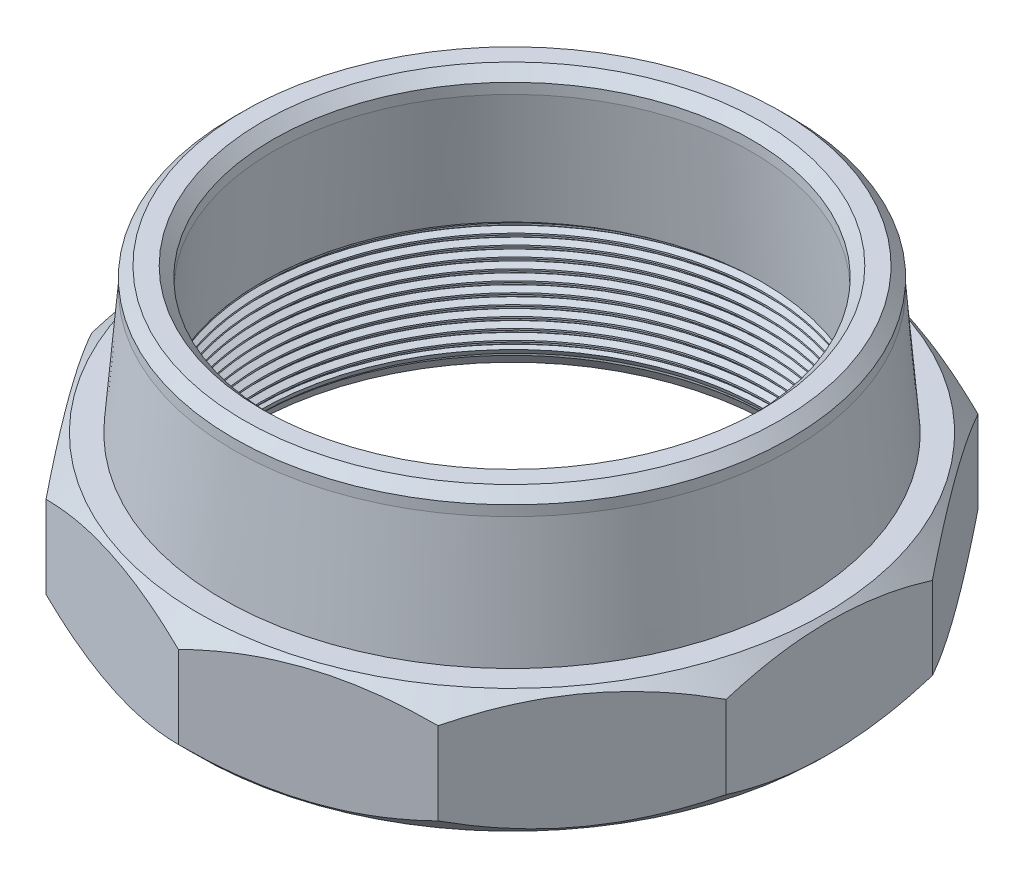
SolidWorks part; units mm, degrees
material "ABS"
ref_plane "Спереди" through (0, 0, 0) normal (0, 0, 1) x (1, 0, 0)
ref_plane "Сверху" through (0, 0, 0) normal (0, 1, 0) x (1, 0, 0)
ref_plane "Справа" through (0, 0, 0) normal (1, 0, 0) x (0, 0, -1)
sketch "Эскиз1" plane through (0, 0, 0) normal (0, 0, 1) x (1, 0, 0)
  line L0 (0, 9.0507) -> (0, -9.1503) construction
  line L1 (24.36, -12) -> (24.36, 0.6)
  line L3 (24.36, -12) -> (29.3544, -12)
  line L5 (28, 0) -> (27, 12.0447)
  line L9 (23.2, 14.0447) -> (27, 14.0447)
  line L10 (27, 14.0447) -> (27, 12.0447)
  line L11 (28, 0) -> (30.36, 0)
  line L12 (32.36, -2) -> (32.36, -10)
  line L13 (30.36, -12) -> (29.3544, -12)
  line L14 (30.36, 0) -> (32.36, -2)
  line L15 (32.36, -10) -> (30.36, -12)
  line L18 (24.2, 0.6) -> (23.2, 12.0301)
  line L19 (24.2, 0.6) -> (24.36, 0.6)
  line L20 (23.2, 12.0301) -> (23.2, 14.0447)
  point P13 (23.0817, 14.0447)
  dimension "D2" = 2
  dimension "D3" = 24.36
  dimension "D4" = 2
  dimension "D5" = 45
  dimension "D6" = 45
  dimension "D7" = 24.2
  dimension "D9" = 23.2
  dimension "D10" = 6
  dimension "D11" = 2
  dimension "D12" = 28
  dimension "D13" = 12.6
  dimension "D14" = 12
  dimension "D16" = 27
revolve "Повернуть1" add sketch "Эскиз1" angle 360 about L0
sketch "Эскиз2" plane through (0, 0, 0) normal (0, 1, 0) x (1, 0, 0)
  line L0 (0, 32.36) -> (0, -32.36) construction
  line L10 (0, 32.36) -> (-19.0207, 26.1798)
  line L11 (-19.0207, 26.1798) -> (-30.7762, 9.9998)
  line L12 (-30.7762, 9.9998) -> (-30.7762, -9.9998)
  line L13 (-30.7762, -9.9998) -> (-19.0207, -26.1798)
  line L14 (-19.0207, -26.1798) -> (0, -32.36)
  line L15 (0, -32.36) -> (19.0207, -26.1798)
  line L16 (19.0207, -26.1798) -> (30.7762, -9.9998)
  line L17 (30.7762, -9.9998) -> (30.7762, 9.9998)
  line L18 (30.7762, 9.9998) -> (19.0207, 26.1798)
  line L19 (19.0207, 26.1798) -> (0, 32.36)
  circle A0 centre (0, 0) radius 32.36 construction
  circle A1 centre (0, 0) radius 30.7762 construction
extrude "Вырез-Вытянуть3" cut sketch "Эскиз2" against normal blind 42 flip side to cut
chamfer "Фаска1" distance 2 distance2 1 1 edges at (-24.36, -12, 0) first distance on face at (-24.36, -12, 0)
chamfer "Фаска2" distance 1 angle 45 1 edges at (-27, 14.0447, 0)
sketch "Эскиз3" plane through (0, 0.6, 0) normal (0, -1, 0) x (1, 0, 0)
  circle A0 centre (0, 0) radius 24.36
  dimension "D1" = 48.72
curve "Спираль1" pitch 1 height 19.5 radius 24.36 left hand yes centre (0, 0.6, 0) axis (0, -1, 0) start towards (0, 0, 1)
ref_plane "Плоскость2" through (0, 0, 0) normal (-1, 0, 0) x (0, 0, 1)
sketch "Эскиз4" plane through (0, 0, 0) normal (-1, 0, 0) x (0, 0, 1)
  line L4 (-24.36, -19.325) -> (-24.36, -18.475) construction
  line L5 (-24.36, -18.475) -> (-24.8796, -18.775)
  line L6 (-24.8796, -18.775) -> (-24.8796, -19.025) construction
  line L7 (-24.8796, -19.025) -> (-24.36, -19.325)
  line L8 (-24.36, -18.9) -> (-24.8796, -18.9) construction
  line L9 (-24.8796, -18.775) -> (-24.9096, -18.775)
  line L10 (-24.9096, -18.775) -> (-24.9096, -19.025)
  line L11 (-24.9096, -19.025) -> (-24.8796, -19.025)
  line L12 (-24.36, -18.475) -> (-24.26, -18.4173)
  line L13 (-24.26, -18.4173) -> (-24.26, -19.3827)
  line L14 (-24.26, -19.3827) -> (-24.36, -19.325)
  line L15 (0, 0) -> (0, -30) construction
  spline S1 degree 3 poles (24.36, 0.6) (24.36, 0.5848) (23.6837, 0.5542) (20.7235, 0.5085) (16.0609, 0.4627) (10.0789, 0.4169) (3.2689, 0.3711) (-3.8097, 0.3254) (-10.5753, 0.2796) (-16.4721, 0.2338) (-21.0157, 0.188) (-23.8329, 0.1423) (-24.6921, 0.0965) (-23.5229, 0.0507) (-20.4212, 0.0049) (-15.6419, -0.0408) (-9.5776, -0.0866) (-2.7265, -0.1324) (4.3486, -0.1782) (11.0664, -0.2239) (16.8752, -0.2697) (21.2976, -0.3155) (23.9704, -0.3613) (24.674, -0.407) (23.3506, -0.4528) (20.1089, -0.4986) (15.2153, -0.5444) (9.0717, -0.5901) (2.1828, -0.6359) (-4.8853, -0.6817) (-11.5522, -0.7275) (-17.27, -0.7732) (-21.569, -0.819) (-24.0962, -0.8648) (-24.6438, -0.9106) (-23.1669, -0.9563) (-19.7868, -1.0021) (-14.7812, -1.0479) (-8.5613, -1.0937) (-1.6381, -1.1394) (5.4197, -1.1852) (12.0323, -1.231) (17.6564, -1.2768) (21.8299, -1.3225) (24.2102, -1.3683) (24.6015, -1.4141) (22.9718, -1.4599) (19.4549, -1.5056) (14.3398, -1.5514) (8.0467, -1.5972) (1.0925, -1.643) (-5.9515, -1.6887) (-12.5065, -1.7345) (-18.0341, -1.7803) (-22.0802, -1.8261) (-24.3123, -1.8718) (-24.5472, -1.9176) (-22.7655, -1.9634) (-19.1136, -2.0092) (-13.8915, -2.0549) (-7.5281, -2.1007) (-0.5464, -2.1465) (6.4803, -2.1923) (12.9746, -2.238) (18.403, -2.2838) (22.3196, -2.3296) (24.4026, -2.3754) (24.4809, -2.4211) (22.5481, -2.4669) (18.7629, -2.5127) (13.4363, -2.5585) (7.0059, -2.6042) (0, -2.65) (-7.0059, -2.6958) (-13.4363, -2.7415) (-18.7629, -2.7873) (-22.5481, -2.8331) (-24.4809, -2.8789) (-24.4026, -2.9246) (-22.3196, -2.9704) (-18.403, -3.0162) (-12.9746, -3.062) (-6.4803, -3.1077) (0.5464, -3.1535) (7.5281, -3.1993) (13.8915, -3.2451) (19.1136, -3.2908) (22.7655, -3.3366) (24.5472, -3.3824) (24.3123, -3.4282) (22.0802, -3.4739) (18.0341, -3.5197) (12.5065, -3.5655) (5.9515, -3.6113) (-1.0925, -3.657) (-8.0467, -3.7028) (-14.3398, -3.7486) (-19.4549, -3.7944) (-22.9718, -3.8401) (-24.6015, -3.8859) (-24.2102, -3.9317) (-21.8299, -3.9775) (-17.6564, -4.0232) (-12.0323, -4.069) (-5.4197, -4.1148) (1.6381, -4.1606) (8.5613, -4.2063) (14.7812, -4.2521) (19.7868, -4.2979) (23.1669, -4.3437) (24.6438, -4.3894) (24.0962, -4.4352) (21.569, -4.481) (17.27, -4.5268) (11.5522, -4.5725) (4.8853, -4.6183) (-2.1828, -4.6641) (-9.0717, -4.7099) (-15.2153, -4.7556) (-20.1089, -4.8014) (-23.3506, -4.8472) (-24.674, -4.893) (-23.9704, -4.9387) (-21.2976, -4.9845) (-16.8752, -5.0303) (-11.0664, -5.0761) (-4.3486, -5.1218) (2.7265, -5.1676) (9.5776, -5.2134) (15.6419, -5.2592) (20.4212, -5.3049) (23.5229, -5.3507) (24.6921, -5.3965) (23.8329, -5.4423) (21.0157, -5.488) (16.4721, -5.5338) (10.5753, -5.5796) (3.8097, -5.6254) (-3.2689, -5.6711) (-10.0789, -5.7169) (-16.0609, -5.7627) (-20.7235, -5.8085) (-23.6837, -5.8542) (-24.6982, -5.9) (-23.6837, -5.9458) (-20.7235, -5.9915) (-16.0609, -6.0373) (-10.0789, -6.0831) (-3.2689, -6.1289) (3.8097, -6.1746) (10.5753, -6.2204) (16.4721, -6.2662) (21.0157, -6.312) (23.8329, -6.3577) (24.6921, -6.4035) (23.5229, -6.4493) (20.4212, -6.4951) (15.6419, -6.5408) (9.5776, -6.5866) (2.7265, -6.6324) (-4.3486, -6.6782) (-11.0664, -6.7239) (-16.8752, -6.7697) (-21.2976, -6.8155) (-23.9704, -6.8613) (-24.674, -6.907) (-23.3506, -6.9528) (-20.1089, -6.9986) (-15.2153, -7.0444) (-9.0717, -7.0901) (-2.1828, -7.1359) (4.8853, -7.1817) (11.5522, -7.2275) (17.27, -7.2732) (21.569, -7.319) (24.0962, -7.3648) (24.6438, -7.4106) (23.1669, -7.4563) (19.7868, -7.5021) (14.7812, -7.5479) (8.5613, -7.5937) (1.6381, -7.6394) (-5.4197, -7.6852) (-12.0323, -7.731) (-17.6564, -7.7768) (-21.8299, -7.8225) (-24.2102, -7.8683) (-24.6015, -7.9141) (-22.9718, -7.9599) (-19.4549, -8.0056) (-14.3398, -8.0514) (-8.0467, -8.0972) (-1.0925, -8.143) (5.9515, -8.1887) (12.5065, -8.2345) (18.0341, -8.2803) (22.0802, -8.3261) (24.3123, -8.3718) (24.5472, -8.4176) (22.7655, -8.4634) (19.1136, -8.5092) (13.8915, -8.5549) (7.5281, -8.6007) (0.5464, -8.6465) (-6.4803, -8.6923) (-12.9746, -8.738) (-18.403, -8.7838) (-22.3196, -8.8296) (-24.4026, -8.8754) (-24.4809, -8.9211) (-22.5481, -8.9669) (-18.7629, -9.0127) (-13.4363, -9.0585) (-7.0059, -9.1042) (0, -9.15) (7.0059, -9.1958) (13.4363, -9.2415) (18.7629, -9.2873) (22.5481, -9.3331) (24.4809, -9.3789) (24.4026, -9.4246) (22.3196, -9.4704) (18.403, -9.5162) (12.9746, -9.562) (6.4803, -9.6077) (-0.5464, -9.6535) (-7.5281, -9.6993) (-13.8915, -9.7451) (-19.1136, -9.7908) (-22.7655, -9.8366) (-24.5472, -9.8824) (-24.3123, -9.9282) (-22.0802, -9.9739) (-18.0341, -10.0197) (-12.5065, -10.0655) (-5.9515, -10.1113) (1.0925, -10.157) (8.0467, -10.2028) (14.3398, -10.2486) (19.4549, -10.2944) (22.9718, -10.3401) (24.6015, -10.3859) (24.2102, -10.4317) (21.8299, -10.4775) (17.6564, -10.5232) (12.0323, -10.569) (5.4197, -10.6148) (-1.6381, -10.6606) (-8.5613, -10.7063) (-14.7812, -10.7521) (-19.7868, -10.7979) (-23.1669, -10.8437) (-24.6438, -10.8894) (-24.0962, -10.9352) (-21.569, -10.981) (-17.27, -11.0268) (-11.5522, -11.0725) (-4.8853, -11.1183) (2.1828, -11.1641) (9.0717, -11.2099) (15.2153, -11.2556) (20.1089, -11.3014) (23.3506, -11.3472) (24.674, -11.393) (23.9704, -11.4387) (21.2976, -11.4845) (16.8752, -11.5303) (11.0664, -11.5761) (4.3486, -11.6218) (-2.7265, -11.6676) (-9.5776, -11.7134) (-15.6419, -11.7592) (-20.4212, -11.8049) (-23.5229, -11.8507) (-24.6921, -11.8965) (-23.8329, -11.9423) (-21.0157, -11.988) (-16.4721, -12.0338) (-10.5753, -12.0796) (-3.8097, -12.1254) (3.2689, -12.1711) (10.0789, -12.2169) (16.0609, -12.2627) (20.7235, -12.3085) (23.6837, -12.3542) (24.6982, -12.4) (23.6837, -12.4458) (20.7235, -12.4915) (16.0609, -12.5373) (10.0789, -12.5831) (3.2689, -12.6289) (-3.8097, -12.6746) (-10.5753, -12.7204) (-16.4721, -12.7662) (-21.0157, -12.812) (-23.8329, -12.8577) (-24.6921, -12.9035) (-23.5229, -12.9493) (-20.4212, -12.9951) (-15.6419, -13.0408) (-9.5776, -13.0866) (-2.7265, -13.1324) (4.3486, -13.1782) (11.0664, -13.2239) (16.8752, -13.2697) (21.2976, -13.3155) (23.9704, -13.3613) (24.674, -13.407) (23.3506, -13.4528) (20.1089, -13.4986) (15.2153, -13.5444) (9.0717, -13.5901) (2.1828, -13.6359) (-4.8853, -13.6817) (-11.5522, -13.7275) (-17.27, -13.7732) (-21.569, -13.819) (-24.0962, -13.8648) (-24.6438, -13.9106) (-23.1669, -13.9563) (-19.7868, -14.0021) (-14.7812, -14.0479) (-8.5613, -14.0937) (-1.6381, -14.1394) (5.4197, -14.1852) (12.0323, -14.231) (17.6564, -14.2768) (21.8299, -14.3225) (24.2102, -14.3683) (24.6015, -14.4141) (22.9718, -14.4599) (19.4549, -14.5056) (14.3398, -14.5514) (8.0467, -14.5972) (1.0925, -14.643) (-5.9515, -14.6887) (-12.5065, -14.7345) (-18.0341, -14.7803) (-22.0802, -14.8261) (-24.3123, -14.8718) (-24.5472, -14.9176) (-22.7655, -14.9634) (-19.1136, -15.0092) (-13.8915, -15.0549) (-7.5281, -15.1007) (-0.5464, -15.1465) (6.4803, -15.1923) (12.9746, -15.238) (18.403, -15.2838) (22.3196, -15.3296) (24.4026, -15.3754) (24.4809, -15.4211) (22.5481, -15.4669) (18.7629, -15.5127) (13.4363, -15.5585) (7.0059, -15.6042) (0, -15.65) (-7.0059, -15.6958) (-13.4363, -15.7415) (-18.7629, -15.7873) (-22.5481, -15.8331) (-24.4809, -15.8789) (-24.4026, -15.9246) (-22.3196, -15.9704) (-18.403, -16.0162) (-12.9746, -16.062) (-6.4803, -16.1077) (0.5464, -16.1535) (7.5281, -16.1993) (13.8915, -16.2451) (19.1136, -16.2908) (22.7655, -16.3366) (24.5472, -16.3824) (24.3123, -16.4282) (22.0802, -16.4739) (18.0341, -16.5197) (12.5065, -16.5655) (5.9515, -16.6113) (-1.0925, -16.657) (-8.0467, -16.7028) (-14.3398, -16.7486) (-19.4549, -16.7944) (-22.9718, -16.8401) (-24.6015, -16.8859) (-24.2102, -16.9317) (-21.8299, -16.9775) (-17.6564, -17.0232) (-12.0323, -17.069) (-5.4197, -17.1148) (1.6381, -17.1606) (8.5613, -17.2063) (14.7812, -17.2521) (19.7868, -17.2979) (23.1669, -17.3437) (24.6438, -17.3894) (24.0962, -17.4352) (21.569, -17.481) (17.27, -17.5268) (11.5522, -17.5725) (4.8853, -17.6183) (-2.1828, -17.6641) (-9.0717, -17.7099) (-15.2153, -17.7556) (-20.1089, -17.8014) (-23.3506, -17.8472) (-24.674, -17.893) (-23.9704, -17.9387) (-21.2976, -17.9845) (-16.8752, -18.0303) (-11.0664, -18.0761) (-4.3486, -18.1218) (2.7265, -18.1676) (9.5776, -18.2134) (15.6419, -18.2592) (20.4212, -18.3049) (23.5229, -18.3507) (24.6921, -18.3965) (23.8329, -18.4423) (21.0157, -18.488) (16.4721, -18.5338) (10.5753, -18.5796) (3.8097, -18.6254) (-3.2689, -18.6711) (-10.0789, -18.7169) (-16.0609, -18.7627) (-20.7235, -18.8085) (-23.6837, -18.8542) (-24.36, -18.8848) (-24.36, -18.9) knots 0 0 0 0 0.002347 0.004695 0.007042 0.00939 0.011737 0.014085 0.016432 0.018779 0.021127 0.023474 0.025822 0.028169 0.030516 0.032864 0.035211 0.037559 0.039906 0.042254 0.044601 0.046948 0.049296 0.051643 0.053991 0.056338 0.058685 0.061033 0.06338 0.065728 0.068075 0.070423 0.07277 0.075117 0.077465 0.079812 0.08216 0.084507 0.086854 0.089202 0.091549 0.093897 0.096244 0.098592 0.100939 0.103286 0.105634 0.107981 0.110329 0.112676 0.115023 0.117371 0.119718 0.122066 0.124413 0.126761 0.129108 0.131455 0.133803 0.13615 0.138498 0.140845 0.143192 0.14554 0.147887 0.150235 0.152582 0.15493 0.157277 0.159624 0.161972 0.164319 0.166667 0.169014 0.171362 0.173709 0.176056 0.178404 0.180751 0.183099 0.185446 0.187793 0.190141 0.192488 0.194836 0.197183 0.199531 0.201878 0.204225 0.206573 0.20892 0.211268 0.213615 0.215962 0.21831 0.220657 0.223005 0.225352 0.2277 0.230047 0.232394 0.234742 0.237089 0.239437 0.241784 0.244131 0.246479 0.248826 0.251174 0.253521 0.255869 0.258216 0.260563 0.262911 0.265258 0.267606 0.269953 0.2723 0.274648 0.276995 0.279343 0.28169 0.284038 0.286385 0.288732 0.29108 0.293427 0.295775 0.298122 0.300469 0.302817 0.305164 0.307512 0.309859 0.312207 0.314554 0.316901 0.319249 0.321596 0.323944 0.326291 0.328638 0.330986 0.333333 0.335681 0.338028 0.340376 0.342723 0.34507 0.347418 0.349765 0.352113 0.35446 0.356808 0.359155 0.361502 0.36385 0.366197 0.368545 0.370892 0.373239 0.375587 0.377934 0.380282 0.382629 0.384977 0.387324 0.389671 0.392019 0.394366 0.396714 0.399061 0.401408 0.403756 0.406103 0.408451 0.410798 0.413146 0.415493 0.41784 0.420188 0.422535 0.424883 0.42723 0.429577 0.431925 0.434272 0.43662 0.438967 0.441315 0.443662 0.446009 0.448357 0.450704 0.453052 0.455399 0.457746 0.460094 0.462441 0.464789 0.467136 0.469484 0.471831 0.474178 0.476526 0.478873 0.481221 0.483568 0.485915 0.488263 0.49061 0.492958 0.495305 0.497653 0.5 0.502347 0.504695 0.507042 0.50939 0.511737 0.514085 0.516432 0.518779 0.521127 0.523474 0.525822 0.528169 0.530516 0.532864 0.535211 0.537559 0.539906 0.542254 0.544601 0.546948 0.549296 0.551643 0.553991 0.556338 0.558685 0.561033 0.56338 0.565728 0.568075 0.570423 0.57277 0.575117 0.577465 0.579812 0.58216 0.584507 0.586854 0.589202 0.591549 0.593897 0.596244 0.598592 0.600939 0.603286 0.605634 0.607981 0.610329 0.612676 0.615023 0.617371 0.619718 0.622066 0.624413 0.626761 0.629108 0.631455 0.633803 0.63615 0.638498 0.640845 0.643192 0.64554 0.647887 0.650235 0.652582 0.65493 0.657277 0.659624 0.661972 0.664319 0.666667 0.669014 0.671362 0.673709 0.676056 0.678404 0.680751 0.683099 0.685446 0.687793 0.690141 0.692488 0.694836 0.697183 0.699531 0.701878 0.704225 0.706573 0.70892 0.711268 0.713615 0.715962 0.71831 0.720657 0.723005 0.725352 0.7277 0.730047 0.732394 0.734742 0.737089 0.739437 0.741784 0.744131 0.746479 0.748826 0.751174 0.753521 0.755869 0.758216 0.760563 0.762911 0.765258 0.767606 0.769953 0.7723 0.774648 0.776995 0.779343 0.78169 0.784038 0.786385 0.788732 0.79108 0.793427 0.795775 0.798122 0.800469 0.802817 0.805164 0.807512 0.809859 0.812207 0.814554 0.816901 0.819249 0.821596 0.823944 0.826291 0.828638 0.830986 0.833333 0.835681 0.838028 0.840376 0.842723 0.84507 0.847418 0.849765 0.852113 0.85446 0.856808 0.859155 0.861502 0.86385 0.866197 0.868545 0.870892 0.873239 0.875587 0.877934 0.880282 0.882629 0.884977 0.887324 0.889671 0.892019 0.894366 0.896714 0.899061 0.901408 0.903756 0.906103 0.908451 0.910798 0.913146 0.915493 0.91784 0.920188 0.922535 0.924883 0.92723 0.929577 0.931925 0.934272 0.93662 0.938967 0.941315 0.943662 0.946009 0.948357 0.950704 0.953052 0.955399 0.957746 0.960094 0.962441 0.964789 0.967136 0.969484 0.971831 0.974178 0.976526 0.978873 0.981221 0.983568 0.985915 0.988263 0.99061 0.992958 0.995305 0.997653 1 1 1 1 construction
  dimension "D1" = 0.85
  dimension "D2" = 0.25
  dimension "D3" = 60
  dimension "D4" = 0.03
  dimension "D5" = 0.1
sweep "Вырез-По траектории1" cut profiles "Эскиз4" path "Спираль1" align with end faces yes
chamfer "Фаска3" distance 1 angle 45 1 edges at (-23.2, 14.0447, 0)
